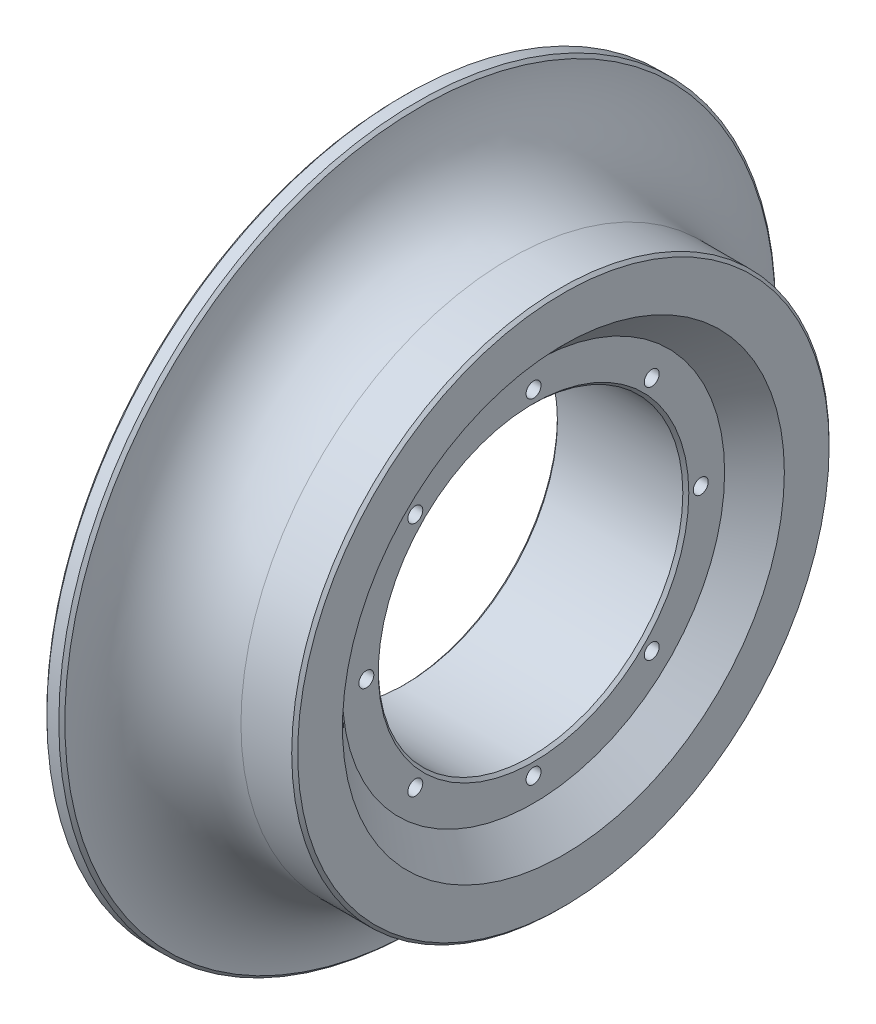
SolidWorks part; units mm, degrees
material "PVC Sztywny"
ref_plane "Płaszczyzna przednia" through (0, 0, 0) normal (0, 0, 1) x (1, 0, 0)
ref_plane "Płaszczyzna górna" through (0, 0, 0) normal (0, 1, 0) x (1, 0, 0)
ref_plane "Płaszczyzna prawa" through (0, 0, 0) normal (1, 0, 0) x (0, 0, -1)
sketch "Szkic1" plane through (0, 0, 0) normal (0, 0, 1) x (1, 0, 0)
  line L2 (-21, 51) -> (21, 51)
  line L3 (-17, 120) -> (-15.9827, 118.9827)
  line L4 (32, 74) -> (22, 64)
  line L5 (14, 90) -> (31, 90)
  line L6 (31, 90) -> (32, 89)
  line L7 (-22, 52) -> (-21, 51)
  line L8 (-17, 120) -> (-21, 120)
  line L9 (21, 51) -> (22, 52)
  line L10 (-22, 119) -> (-22, 52)
  line L11 (32, 89) -> (32, 74)
  line L12 (-22, 119) -> (-21, 120)
  line L13 (22, 52) -> (22, 64)
  line L14 (0, 0) -> (-48.9401, 0) construction
  arc A0 (-15.9827, 118.9827) -> (14, 90) centre (14, 120) ccw
revolve "Obrót1" add sketch "Szkic1" angle 360 about L14
sketch "Szkic2" plane through (-22, 0, 0) normal (-1, 0, 0) x (0, 0, 1)
  circle A0 centre (0, 56) radius 2.5
  circle A1 centre (39.598, 39.598) radius 2.5
  circle A2 centre (56, 0) radius 2.5
  circle A3 centre (39.598, -39.598) radius 2.5
  circle A4 centre (0, -56) radius 2.5
  circle A5 centre (-39.598, -39.598) radius 2.5
  circle A6 centre (-56, 0) radius 2.5
  circle A7 centre (-39.598, 39.598) radius 2.5
  point P20 (0, 0)
  dimension "D1" = 5
  dimension "D2" = 56
  dimension "D3" = 8
extrude "Wytnij-wyciągnięcie1" cut sketch "Szkic2" against normal through all
